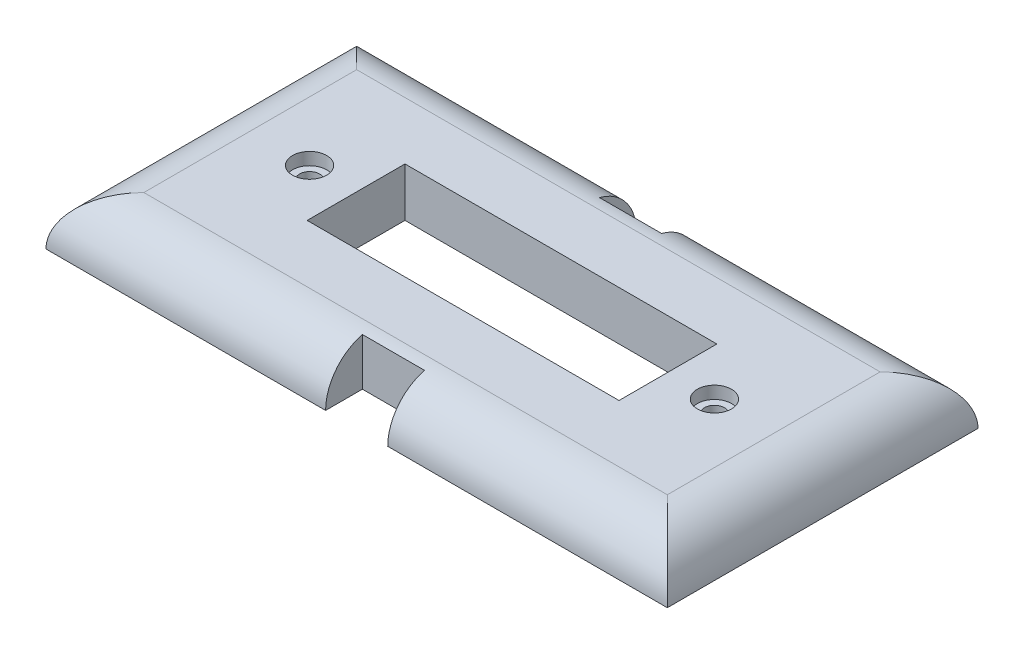
SolidWorks part; units mm, degrees
ref_plane "Front Plane" through (0, 0, 0) normal (0, 0, 1) x (1, 0, 0)
ref_plane "Top Plane" through (0, 0, 0) normal (0, 1, 0) x (1, 0, 0)
ref_plane "Right Plane" through (0, 0, 0) normal (1, 0, 0) x (0, 0, -1)
sketch "Sketch2" plane through (0, 0, 0) normal (0, 1, 0) x (1, 0, 0)
  line L1 (-50.8, -25.4) -> (50.8, -25.4)
  line L2 (-50.8, -25.4) -> (-50.8, 25.4)
  line L3 (-50.8, 25.4) -> (50.8, 25.4)
  line L4 (50.8, -25.4) -> (50.8, 25.4)
  line L5 (-50.8, -25.4) -> (50.8, 25.4) construction
  line L6 (-50.8, 25.4) -> (50.8, -25.4) construction
  point P0 (0, 0)
  dimension "D1" = 50.8
  dimension "D2" = 101.6
extrude "Boss-Extrude1" add sketch "Sketch2" along normal blind 8
sketch "Sketch3" plane through (0, 8, 0) normal (0, 1, 0) x (1, 0, 0)
  line L1 (-25.5, -8) -> (25.5, -8)
  line L2 (-25.5, -8) -> (-25.5, 8)
  line L3 (-25.5, 8) -> (25.5, 8)
  line L4 (25.5, -8) -> (25.5, 8)
  line L5 (-25.5, -8) -> (25.5, 8) construction
  line L6 (-25.5, 8) -> (25.5, -8) construction
  point P0 (0, 0)
  dimension "D1" = 16
  dimension "D2" = 51
extrude "Cut-Extrude1" cut sketch "Sketch3" against normal through all
fillet "Fillet1" radius 8 4 edges at (0, 8, -25.4) (50.8, 8, 0) (0, 8, 25.4) (-50.8, 8, 0)
sketch "Sketch5" plane through (0, 0, 0) normal (0, -1, 0) x (1, 0, 0)
  circle A0 centre (-33.1, 0) radius 1.6319
  dimension "D1" = 3.2639
extrude "Cut-Extrude2" cut sketch "Sketch5" against normal through all
sketch "Sketch6" plane through (0, 0, 0) normal (0, -1, 0) x (1, 0, 0)
  circle A0 centre (33.1, 0) radius 1.6319
  dimension "D1" = 3.2639
extrude "Cut-Extrude3" cut sketch "Sketch6" against normal through all
sketch "Sketch7" plane through (0, 0, 0) normal (0, -1, 0) x (1, 0, 0)
  line L0 (-50.8, 25.4) -> (50.8, 25.4) construction
  line L1 (5.08, 19.384) -> (-5.08, 19.384)
  line L2 (5.08, 19.384) -> (5.08, 25.4)
  line L3 (5.08, 25.4) -> (-5.08, 25.4)
  line L4 (-5.08, 19.384) -> (-5.08, 25.4)
  line L5 (5.08, 19.384) -> (-5.08, 25.4) construction
  line L6 (5.08, 25.4) -> (-5.08, 19.384) construction
  point P0 (0, 22.392)
  dimension "D1" = 10.16
  dimension "D2" = 6.016
extrude "Cut-Extrude4" cut sketch "Sketch7" against normal through all
sketch "Sketch8" plane through (0, 0, 0) normal (0, -1, 0) x (1, 0, 0)
  line L0 (50.8, -25.4) -> (-50.8, -25.4) construction
  line L1 (5.08, -19.384) -> (-5.08, -19.384)
  line L2 (5.08, -19.384) -> (5.08, -25.4)
  line L3 (5.08, -25.4) -> (-5.08, -25.4)
  line L4 (-5.08, -19.384) -> (-5.08, -25.4)
  line L5 (5.08, -19.384) -> (-5.08, -25.4) construction
  line L6 (5.08, -25.4) -> (-5.08, -19.384) construction
  point P0 (0, -22.392)
  dimension "D1" = 6.016
  dimension "D2" = 10.16
extrude "Cut-Extrude5" cut sketch "Sketch8" against normal through all
sketch "Sketch9" plane through (0, 8, 0) normal (0, 1, 0) x (1, 0, 0)
  circle A0 centre (-33.1, 0) radius 2.794
  dimension "D1" = 5.588
extrude "Cut-Extrude6" cut sketch "Sketch9" against normal blind 2.032
sketch "Sketch10" plane through (0, 8, 0) normal (0, 1, 0) x (1, 0, 0)
  circle A0 centre (33.1, 0) radius 2.794
  dimension "D1" = 5.588
extrude "Cut-Extrude7" cut sketch "Sketch10" against normal blind 2.032
